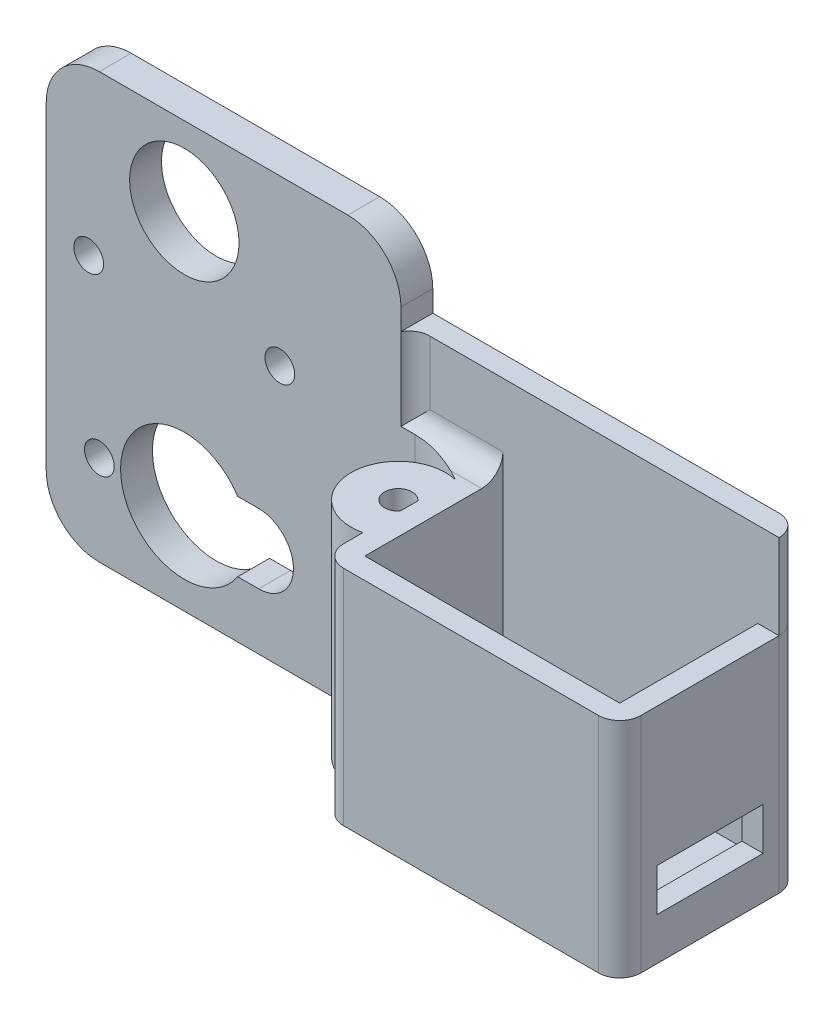
SolidWorks part; units mm, degrees
ref_plane "前视基准面" through (0, 0, 0) normal (0, 0, 1) x (1, 0, 0)
ref_plane "上视基准面" through (0, 0, 0) normal (0, 1, 0) x (1, 0, 0)
ref_plane "右视基准面" through (0, 0, 0) normal (1, 0, 0) x (0, 0, -1)
sketch "草图1" plane through (0, 0, 0) normal (0, 1, 0) x (1, 0, 0)
  line L5 (-14, 8.5) -> (14, 8.5)
  line L6 (-14, 8.5) -> (-14, -8.5)
  line L7 (-14, -8.5) -> (14, -8.5)
  line L8 (14, 8.5) -> (14, -8.5)
  dimension "D5" = 28
  dimension "D8" = 17
extrude "凸台-拉伸1" add sketch "草图1" along normal blind 21
shell "抽壳1" thickness 2
sketch "草图2" plane through (0, 21, 0) normal (0, 1, 0) x (1, 0, 0)
  line L0 (-12, 6.5) -> (-12, -6.5) construction
  line L1 (-12.0019, 2.9482) -> (-12, -3.6346)
  line L2 (-12, 6.5) -> (-12, -6.5) construction
  circle A0 centre (-15, -0.3441) radius 1.3
  arc A1 (-12.0019, 2.9482) -> (-12, -3.6346) centre (-15, -0.3441) ccw
  dimension "D1" = 3
extrude "凸台-拉伸2" add sketch "草图2" against normal blind 21
fillet "圆角1" radius 2 4 edges at (14, 10.5, 8.5) (-14, 10.5, 8.5) (-14, 10.5, -8.5) (14, 10.5, -8.5)
sketch "草图8" plane through (14, 0, 0) normal (1, 0, 0) x (0, 0, -1)
  line L0 (-6.5, 0) -> (6.5, 0) construction
  line L1 (-5, 8) -> (5, 8)
  line L2 (-5, 8) -> (-5, 4)
  line L3 (-5, 4) -> (5, 4)
  line L4 (5, 8) -> (5, 4)
  dimension "D1" = 10
  dimension "D2" = 4
  dimension "D3" = 5
  dimension "D4" = 4
extrude "切除-拉伸2" cut sketch "草图8" against normal blind 4
sketch "草图9" plane through (0, 0, 0) normal (0, -1, 0) x (1, 0, 0)
  line L1 (-14, -0.4866) -> (-14, 1.1747) construction
  circle A0 centre (4.5, 0) radius 1.4
  dimension "D1" = 18.5
extrude "切除-拉伸3" cut sketch "草图9" against normal blind 4
sketch "草图10" plane through (0, 0, 0) normal (0, -1, 0) x (1, 0, 0)
  line L5 (-14, -6.5) -> (-14, -3.995) construction
  line L6 (-12, -8.5) -> (-54, -8.5)
  line L7 (-12, -8.5) -> (-12, -5.5)
  line L8 (-12, -5.5) -> (-54, -5.5)
  line L9 (-54, -8.5) -> (-54, -5.5)
  arc A0 (-14, -6.5) -> (-12, -8.5) centre (-12, -6.5) ccw construction
  dimension "D1" = 42
  dimension "D2" = 40
  dimension "D3" = 3
extrude "凸台-拉伸3" add sketch "草图10" against normal blind 21
fillet "圆角2" radius 10 1 edges at (-14, 10.5, -5.5)
sketch "草图11" plane through (0, 0, -8.5) normal (0, 0, -1) x (-1, 0, 0)
  line L0 (54, 21) -> (54, 0) construction
  line L1 (-12, 0) -> (54, 0) construction
  circle A0 centre (49, 4.5) radius 1.4
  circle A1 centre (22, 4.5) radius 1.4
  dimension "D1" = 5
  dimension "D2" = 27
  dimension "D3" = 4.5
extrude "切除-拉伸4" cut sketch "草图11" against normal blind 21
sketch "草图12" plane through (0, 0, -8.5) normal (0, 0, -1) x (-1, 0, 0)
  line L0 (34, 7.1) -> (35.5456, 7.1)
  line L1 (34, 2.1) -> (35.5456, 2.1)
  line L2 (54, 21) -> (54, 0) construction
  line L3 (-12, 0) -> (54, 0) construction
  arc A0 (35.5456, 2.1) -> (35.5456, 7.1) centre (41, 4.6) ccw
  arc A2 (34, 7.1) -> (34, 2.1) centre (34, 4.6) ccw
  dimension "D1" = 13
  dimension "D3" = 12
  dimension "D4" = 5
  dimension "D2" = 7
  dimension "D5" = 4.6
extrude "切除-拉伸5" cut sketch "草图12" against normal blind 21
sketch "草图13" plane through (0, 0, -8.5) normal (0, 0, -1) x (-1, 0, 0)
  line L0 (-12, 21) -> (54, 21) construction
  line L1 (20.6, 21) -> (54, 21)
  line L2 (20.6, 21) -> (20.6, 36)
  line L3 (20.6, 36) -> (54, 36)
  line L4 (54, 21) -> (54, 36)
  dimension "D1" = 15
extrude "凸台-拉伸4" add sketch "草图13" against normal blind 3
fillet "圆角4" radius 5 2 edges at (-54, 36, -7) (-20.6, 36, -7)
sketch "草图14" plane through (0, 0, -8.5) normal (0, 0, -1) x (-1, 0, 0)
  circle A0 centre (41, 28.6) radius 5.15
  arc A1 (35.5456, 2.1) -> (37.1477, 0) centre (41, 4.6) ccw construction
  dimension "D1" = 24
extrude "切除-拉伸6" cut sketch "草图14" against normal blind 3
sketch "草图15" plane through (0, 0, -8.5) normal (0, 0, -1) x (-1, 0, 0)
  line L0 (41, 28.6) -> (41, 4.6) construction
  line L1 (54, 31) -> (54, 0) construction
  circle A0 centre (50, 20.5014) radius 1.4
  circle A1 centre (32, 20.5014) radius 1.4
  dimension "D1" = 2.8
  dimension "D2" = 4
extrude "切除-拉伸7" cut sketch "草图15" against normal blind 3
sketch "草图18" plane through (0, 0, -8.5) normal (0, 0, -1) x (-1, 0, 0)
  line L0 (-12, 0) -> (37.1477, 0) construction
  line L1 (20.6, 0) -> (54, 0)
  line L2 (20.6, 0) -> (20.6, -4)
  line L3 (20.6, -4) -> (54, -4)
  line L4 (54, 0) -> (54, -4)
  dimension "D1" = 4
extrude "凸台-拉伸5" add sketch "草图18" against normal blind 3
sketch "草图19" plane through (0, 0, -8.5) normal (0, 0, -1) x (-1, 0, 0)
  line L0 (34, 7.8748) -> (37.2748, 7.8748)
  line L1 (37.2748, 7.8748) -> (37.1142, 1.3252)
  line L2 (37.1142, 1.3252) -> (34, 1.3252)
  arc A0 (34, 7.8748) -> (34, 1.3252) centre (34, 4.6) ccw
  arc A1 (37.1748, 3.7969) -> (37.2103, 5.2465) centre (34, 4.6) ccw
  arc M22 (37.1477, 0) -> (35.5456, 2.1) centre (41, 4.6) cw
  line M23 (35.5456, 2.1) -> (34, 2.1)
  arc M24 (34, 2.1) -> (34, 7.1) centre (34, 4.6) cw
  line M25 (34, 7.1) -> (35.5456, 7.1)
  arc M26 (35.5456, 7.1) -> (44.8523, 0) centre (41, 4.6) cw
extrude "切除-拉伸8" cut sketch "草图19" against normal blind 3 contours L0 A0 L2 M22 M23 M24 M25 M26 | L2 L1 L0 M26 M25 M24 M23 M22
sketch "草图20" plane through (0, 0, -8.5) normal (0, 0, -1) x (-1, 0, 0)
  circle A0 centre (41, 4.6) radius 6
extrude "切除-拉伸9" cut sketch "草图20" against normal blind 3
fillet "圆角5" radius 5 2 edges at (-20.6, -4, -7) (-54, -4, -7)
sketch "草图21" plane through (0, 21, 0) normal (0, 1, 0) x (1, 0, 0)
  line L1 (-20.6, 8.5) -> (14, 8.5)
  line L2 (-20.6, 8.5) -> (-20.6, 6.5)
  line L3 (-20.6, 6.5) -> (14, 6.5)
  line L4 (14, 8.5) -> (14, 6.5)
extrude "凸台-拉伸6" add sketch "草图21" along normal blind 8
fillet "圆角7" radius 2 3 edges at (14, 25, -8.5) (-16.3, 21, -6.5) (-20.6, 25, -6.5)
